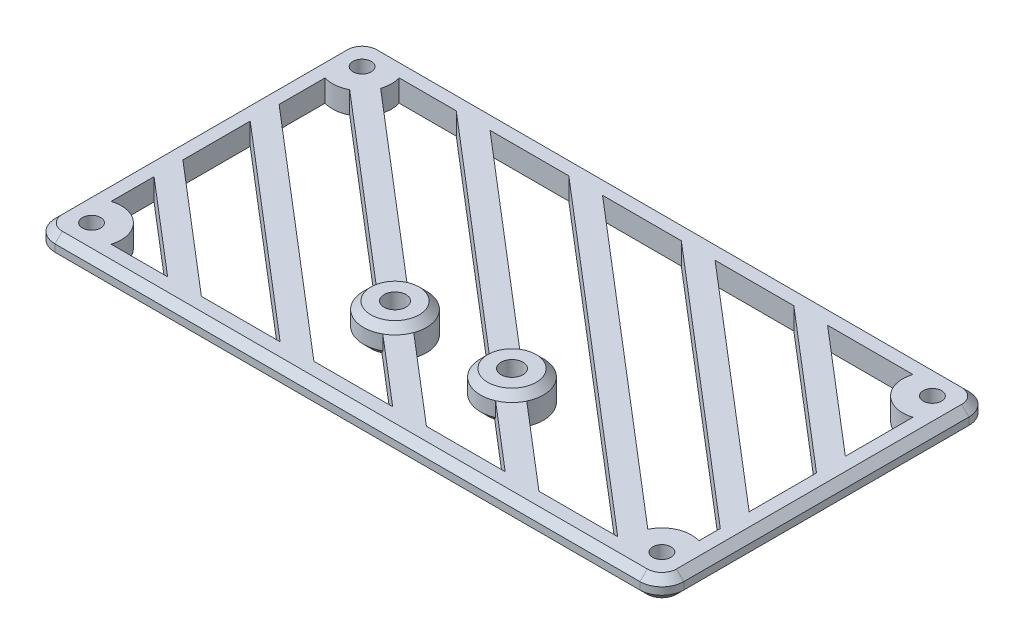
SolidWorks part; units mm, degrees
material "PETG"
ref_plane "Front Plane" through (0, 0, 0) normal (0, 0, 1) x (1, 0, 0)
ref_plane "Top Plane" through (0, 0, 0) normal (0, 1, 0) x (1, 0, 0)
ref_plane "Right Plane" through (0, 0, 0) normal (1, 0, 0) x (0, 0, -1)
sketch "Sketch1" plane through (0, 0, 0) normal (0, 1, 0) x (1, 0, 0)
  line L1 (-39, -18.5) -> (39, -18.5) construction
  line L2 (-39, -18.5) -> (-39, 18.5) construction
  line L3 (-39, 18.5) -> (39, 18.5) construction
  line L4 (39, -18.5) -> (39, 18.5) construction
  line L5 (-39, -18.5) -> (39, 18.5) construction
  line L6 (-39, 18.5) -> (39, -18.5) construction
  line L7 (-43, -22.5) -> (43, -22.5)
  line L8 (-43, -22.5) -> (-43, 22.5)
  line L9 (-43, 22.5) -> (43, 22.5)
  line L10 (43, -22.5) -> (43, 22.5)
  line L11 (-43, -22.5) -> (43, 22.5) construction
  line L12 (-43, 22.5) -> (43, -22.5) construction
  circle A0 centre (-39, 18.5) radius 1.25
  circle A1 centre (39, 18.5) radius 1.25
  circle A2 centre (39, -18.5) radius 1.25
  circle A3 centre (-39, -18.5) radius 1.25
  point P0 (0, 0)
  point P10 (0, 0)
  dimension "D3" = 2.5
  dimension "D1" = 78
  dimension "D2" = 37
  dimension "D4" = 4
  dimension "D5" = 4
extrude "Boss-Extrude1" add sketch "Sketch1" along normal blind 3
fillet "Fillet1" radius 3 4 edges at (-43, 1.5, -22.5) (43, 1.5, -22.5) (43, 1.5, 22.5) (-43, 1.5, 22.5)
sketch "Sketch2" plane through (0, 3, 0) normal (0, 1, 0) x (1, 0, 0)
  line L1 (-8, -8) -> (8, -8) construction
  line L2 (-8, -8) -> (-8, 8) construction
  line L3 (-8, 8) -> (8, 8) construction
  line L4 (8, -8) -> (8, 8) construction
  line L5 (-8, -8) -> (8, 8) construction
  line L6 (-8, 8) -> (8, -8) construction
  circle A2 centre (8, -8) radius 1.5
  circle A3 centre (-8, -8) radius 1.5
  point P0 (0, 0)
  dimension "D3" = 3
  dimension "D1" = 16
  dimension "D2" = 16
extrude "Cut-Extrude1" cut sketch "Sketch2" against normal through all
shell "Shell1" thickness 2.8
sketch "Sketch3" plane through (0, 3, 0) normal (0, 1, 0) x (1, 0, 0)
  line L0 (-39.0894, -7.7352) -> (-27.1751, -17.92)
  line L1 (-1.9238, 1.754) -> (7.2199, 12.4503) construction
  line L2 (-37.2355, 3.8358) -> (-13.7711, -16.2225)
  line L3 (-12.5032, -4.1505) -> (-34.7549, 14.8712)
  line L4 (3.2493, -4.4606) -> (-19.6248, 15.0931)
  line L5 (-3.6696, -11.7018) -> (3.4304, -17.7712)
  line L6 (11.3498, -11.3852) -> (19.7768, -18.5889)
  line L7 (-5.687, 16.3343) -> (32.1276, -15.991)
  line L8 (10.0851, 16.0076) -> (34.7409, -5.0692)
  line L9 (24.6662, 16.6988) -> (36.5865, 6.5089)
  circle A1 centre (-8, -8) radius 4.3 construction
  circle A2 centre (-8, -8) radius 4.3 construction
  arc A3 (-40.2, 14.6319) -> (-35.1319, 19.7) centre (-39, 18.5) ccw construction
  arc A4 (-40.2, 14.6319) -> (-35.1319, 19.7) centre (-39, 18.5) ccw construction
  point P26 (22.413, 5.4692)
  dimension "D1" = 10
  dimension "D2" = 10
  dimension "D3" = 10
  dimension "D4" = 10
  dimension "D5" = 10
  dimension "D6" = 10
rib "Rib1" sketch "Sketch3" sketch "Sketch3" thickness 3 extrusion direction normal to sketch draft on no parameters "D1"=3
sketch "Sketch4" plane through (0, 3, 0) normal (0, 1, 0) x (1, 0, 0)
  line L146 (-27.4013, -19.7) -> (-40.2, -8.7592) construction
  line L147 (-40.2, -8.7592) -> (-40.2, -14.6319) construction
  line L148 (-35.1319, -19.7) -> (-27.4013, -19.7) construction
  line L149 (-12.0115, -19.7) -> (-40.2, 4.3966) construction
  line L150 (-40.2, 4.3966) -> (-40.2, -4.8124) construction
  line L151 (-40.2, -4.8124) -> (-22.7843, -19.7) construction
  line L152 (-22.7843, -19.7) -> (-12.0115, -19.7) construction
  line L153 (3.3783, -19.7) -> (-5.9115, -11.7587) construction
  line L154 (-12.0379, -6.5216) -> (-37.1151, 14.9154) construction
  line L155 (-40.2, 14.6319) -> (-40.2, 8.3434) construction
  line L156 (-40.2, 8.3434) -> (-7.3945, -19.7) construction
  line L157 (-7.3945, -19.7) -> (3.3783, -19.7) construction
  line L158 (18.7681, -19.7) -> (9.7011, -11.9492) construction
  line L159 (3.8342, -6.9339) -> (-27.3224, 19.7) construction
  line L160 (-27.3224, 19.7) -> (-35.1319, 19.7) construction
  line L161 (-35.1658, 17.1957) -> (-10.0885, -4.2413) construction
  line L162 (-3.9621, -9.4784) -> (7.9953, -19.7) construction
  line L163 (7.9953, -19.7) -> (18.7681, -19.7) construction
  line L164 (34.1579, -19.7) -> (-11.9326, 19.7) construction
  line L165 (-11.9326, 19.7) -> (-22.7055, 19.7) construction
  line L166 (-22.7055, 19.7) -> (5.558, -4.4607) construction
  line L167 (11.8761, -9.8617) -> (23.3851, -19.7) construction
  line L168 (23.3851, -19.7) -> (34.1579, -19.7) construction
  line L169 (40.2, -11.7092) -> (3.4571, 19.7) construction
  line L170 (3.4571, 19.7) -> (-7.3157, 19.7) construction
  line L171 (-7.3157, 19.7) -> (35.3407, -16.7644) construction
  line L172 (40.2, -14.6319) -> (40.2, -11.7092) construction
  line L173 (40.2, 1.4466) -> (18.8469, 19.7) construction
  line L174 (18.8469, 19.7) -> (8.0741, 19.7) construction
  line L175 (8.0741, 19.7) -> (40.2, -7.7625) construction
  line L176 (40.2, -7.7625) -> (40.2, 1.4466) construction
  line L177 (35.1319, 19.7) -> (23.4639, 19.7) construction
  line L178 (23.4639, 19.7) -> (40.2, 5.3933) construction
  line L179 (40.2, 5.3933) -> (40.2, 14.6319) construction
  line L180 (-27.4013, -19.7) -> (-40.2, -8.7592)
  line L181 (-40.2, -8.7592) -> (-40.2, -14.6319)
  line L182 (-35.1319, -19.7) -> (-27.4013, -19.7)
  line L183 (-12.0115, -19.7) -> (-40.2, 4.3966)
  line L184 (-40.2, 4.3966) -> (-40.2, -4.8124)
  line L185 (-40.2, -4.8124) -> (-22.7843, -19.7)
  line L186 (-22.7843, -19.7) -> (-12.0115, -19.7)
  line L187 (3.3783, -19.7) -> (-5.9115, -11.7587)
  line L188 (-12.0379, -6.5216) -> (-37.1151, 14.9154)
  line L189 (-40.2, 14.6319) -> (-40.2, 8.3434)
  line L190 (-40.2, 8.3434) -> (-7.3945, -19.7)
  line L191 (-7.3945, -19.7) -> (3.3783, -19.7)
  line L192 (18.7681, -19.7) -> (9.7011, -11.9492)
  line L193 (3.8342, -6.9339) -> (-27.3224, 19.7)
  line L194 (-27.3224, 19.7) -> (-35.1319, 19.7)
  line L195 (-35.1658, 17.1957) -> (-10.0885, -4.2413)
  line L196 (-3.9621, -9.4784) -> (7.9953, -19.7)
  line L197 (7.9953, -19.7) -> (18.7681, -19.7)
  line L198 (34.1579, -19.7) -> (-11.9326, 19.7)
  line L199 (-11.9326, 19.7) -> (-22.7055, 19.7)
  line L200 (-22.7055, 19.7) -> (5.558, -4.4607)
  line L201 (11.8761, -9.8617) -> (23.3851, -19.7)
  line L202 (23.3851, -19.7) -> (34.1579, -19.7)
  line L203 (40.2, -11.7092) -> (3.4571, 19.7)
  line L204 (3.4571, 19.7) -> (-7.3157, 19.7)
  line L205 (-7.3157, 19.7) -> (35.3407, -16.7644)
  line L206 (40.2, -14.6319) -> (40.2, -11.7092)
  line L207 (40.2, 1.4466) -> (18.8469, 19.7)
  line L208 (18.8469, 19.7) -> (8.0741, 19.7)
  line L209 (8.0741, 19.7) -> (40.2, -7.7625)
  line L210 (40.2, -7.7625) -> (40.2, 1.4466)
  line L211 (35.1319, 19.7) -> (23.4639, 19.7)
  line L212 (23.4639, 19.7) -> (40.2, 5.3933)
  line L213 (40.2, 5.3933) -> (40.2, 14.6319)
  arc A46 (-35.1319, -19.7) -> (-40.2, -14.6319) centre (-39, -18.5) ccw construction
  arc A47 (-12.0379, -6.5216) -> (-5.9115, -11.7587) centre (-8, -8) ccw construction
  arc A48 (-40.2, 14.6319) -> (-37.1151, 14.9154) centre (-39, 18.5) ccw construction
  arc A49 (3.8342, -6.9339) -> (9.7011, -11.9492) centre (8, -8) ccw construction
  arc A50 (-35.1658, 17.1957) -> (-35.1319, 19.7) centre (-39, 18.5) ccw construction
  arc A51 (-3.9621, -9.4784) -> (-10.0885, -4.2413) centre (-8, -8) ccw construction
  arc A52 (11.8761, -9.8617) -> (5.558, -4.4607) centre (8, -8) ccw construction
  arc A53 (40.2, -14.6319) -> (35.3407, -16.7644) centre (39, -18.5) ccw construction
  arc A54 (35.1319, 19.7) -> (40.2, 14.6319) centre (39, 18.5) ccw construction
  arc A55 (-35.1319, -19.7) -> (-40.2, -14.6319) centre (-39, -18.5) ccw
  arc A56 (-12.0379, -6.5216) -> (-5.9115, -11.7587) centre (-8, -8) ccw
  arc A57 (-40.2, 14.6319) -> (-37.1151, 14.9154) centre (-39, 18.5) ccw
  arc A58 (3.8342, -6.9339) -> (9.7011, -11.9492) centre (8, -8) ccw
  arc A59 (-35.1658, 17.1957) -> (-35.1319, 19.7) centre (-39, 18.5) ccw
  arc A60 (-3.9621, -9.4784) -> (-10.0885, -4.2413) centre (-8, -8) ccw
  arc A61 (11.8761, -9.8617) -> (5.558, -4.4607) centre (8, -8) ccw
  arc A62 (40.2, -14.6319) -> (35.3407, -16.7644) centre (39, -18.5) ccw
  arc A63 (35.1319, 19.7) -> (40.2, 14.6319) centre (39, 18.5) ccw
extrude "Cut-Extrude2" cut sketch "Sketch4" against normal through all
sketch "Sketch5" plane through (0, 3, 0) normal (0, 1, 0) x (1, 0, 0)
  circle A4 centre (-8, -8) radius 1.5
  circle A5 centre (-8, -8) radius 4.3
  circle A6 centre (8, -8) radius 1.5
  circle A7 centre (8, -8) radius 4.3
extrude "Boss-Extrude2" add sketch "Sketch5" along normal blind 1
chamfer "Chamfer1" distance 1 angle 45 20 edges at (-8, 4, 12.3) (8, 4, 12.3) (-43, 0, 0) (-43, 3, 0) (43, 0, 0) (0, 0, 22.5) (0, 0, -22.5) (-42.1213, 0, 21.6213) (42.1213, 0, 21.6213) (42.1213, 0, -21.6213) (-42.1213, 0, -21.6213) (0, 3, -22.5) (43, 3, 0) (0, 3, 22.5) (-42.1213, 3, 21.6213) (42.1213, 3, 21.6213) (42.1213, 3, -21.6213) (-42.1213, 3, -21.6213) (5.2059, 0, 11.2685) (-10.7941, 0, 11.2685)
